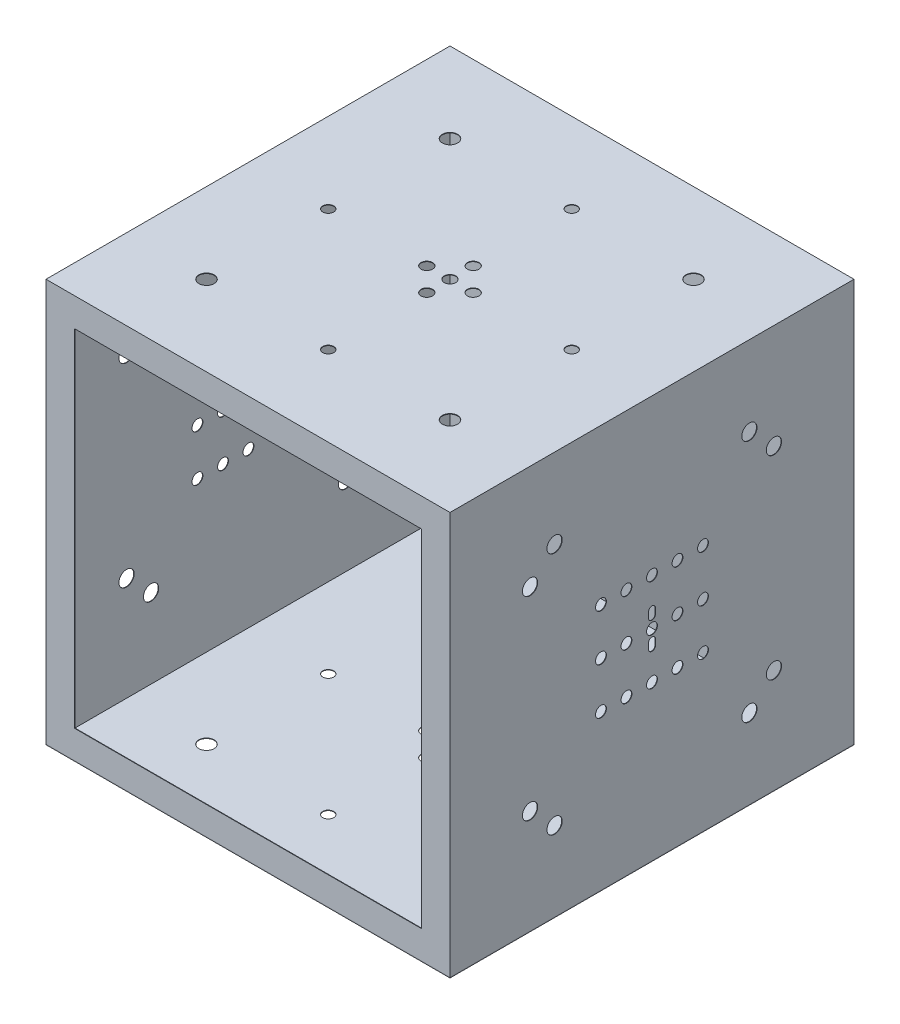
SolidWorks part; units mm, degrees
ref_plane "Front" through (0, 0, 0) normal (0, 0, 1) x (1, 0, 0)
ref_plane "Top" through (0, 0, 0) normal (0, 1, 0) x (1, 0, 0)
ref_plane "Right" through (0, 0, 0) normal (1, 0, 0) x (0, 0, -1)
sketch "Sketch1" plane through (0, 0, 0) normal (0, 0, 1) x (1, 0, 0)
  line L1 (-1742, 1738.5) -> (1742, 1738.5)
  line L2 (-1742, 1738.5) -> (-1742, -1738.5)
  line L3 (-1742, -1738.5) -> (1742, -1738.5)
  line L4 (1742, 1738.5) -> (1742, -1738.5)
  line L5 (-1742, 1738.5) -> (1742, -1738.5) construction
  line L6 (-1742, -1738.5) -> (1742, 1738.5) construction
  point P0 (0, 0)
  dimension "D1" = 3484
  dimension "D2" = 3477
extrude "Boss-Extrude1" add sketch "Sketch1" along normal blind 3484
shell "Shell1" thickness 4 removed face at (0, 0, 3484)
sketch "Sketch2" plane through (0, 0, 3484) normal (0, 0, 1) x (1, 0, 0)
  line L1 (1742, -1738.5) -> (-1742, -1738.5)
  line L2 (1742, -1738.5) -> (1742, 1738.5)
  line L3 (1742, 1738.5) -> (-1742, 1738.5)
  line L4 (-1742, -1738.5) -> (-1742, 1738.5)
  line L5 (1742, -1738.5) -> (-1742, 1738.5) construction
  line L6 (1742, 1738.5) -> (-1742, -1738.5) construction
  line L7 (-1495.5047, -1492.5) -> (1495.5047, -1492.5)
  line L8 (-1495.5047, -1492.5) -> (-1495.5047, 1492.5)
  line L9 (-1495.5047, 1492.5) -> (1495.5047, 1492.5)
  line L10 (1495.5047, -1492.5) -> (1495.5047, 1492.5)
  line L11 (-1495.5047, -1492.5) -> (1495.5047, 1492.5) construction
  line L12 (-1495.5047, 1492.5) -> (1495.5047, -1492.5) construction
  point P0 (0, 0)
  point P7 (0, 0)
  dimension "D1" = 246
extrude "Boss-Extrude2" add sketch "Sketch2" against normal blind 4
sketch "Sketch3" plane through (0, 1738.5, 0) normal (0, 1, 0) x (1, 0, 0)
  line L0 (-1742, -1742) -> (1742, -1742) construction
  line L1 (-1742, -3484) -> (-1742, 0) construction
  line L2 (1742, -3484) -> (1742, 0) construction
  line L3 (0, 0) -> (0, -3484) construction
  line L4 (1742, -3484) -> (-1742, -3484) construction
  line L5 (-1742, 0) -> (0, -1742) construction
  line L6 (0, -1742) -> (-200, -1742) construction
  circle A0 centre (0, -1742) radius 49.85
  circle A1 centre (-200, -1742) radius 49.85
  circle A2 centre (-1050, -1742) radius 46.75
  circle A3 centre (-1050, -692) radius 65.8
  circle A4 centre (1050, -692) radius 65.8
  circle A5 centre (200, -1742) radius 49.85
  circle A6 centre (1050, -1742) radius 46.75
  circle A7 centre (0, -2792) radius 46.75
  circle A8 centre (0, -1942) radius 49.85
  circle A9 centre (0, -1542) radius 49.85
  circle A10 centre (0, -692) radius 46.75
  circle A11 centre (1050, -2792) radius 65.8
  circle A12 centre (-1050, -2792) radius 65.8
  dimension "D1" = 99.7
  dimension "D4" = 93.5
  dimension "D6" = 131.6
  dimension "D3" = 200
  dimension "D5" = 1050
  dimension "D7" = 1050
  dimension "D2" = 2
extrude "Cut-Extrude1" cut sketch "Sketch3" against normal through all
sketch "Sketch4" plane through (0, 0, 0) normal (0, 0, -1) x (-1, 0, 0)
  line L0 (-1742, 0) -> (1742, 0) construction
  line L1 (-1742, -1738.5) -> (-1742, 1738.5) construction
  line L2 (1742, 1738.5) -> (1742, -1738.5) construction
  line L3 (0, 1738.5) -> (0, -1738.5) construction
  line L4 (-1742, 1738.5) -> (1742, 1738.5) construction
  line L5 (1742, -1738.5) -> (-1742, -1738.5) construction
  line L6 (0, 0) -> (-1742, 1738.5) construction
  circle A0 centre (0, 0) radius 91.2
  circle A1 centre (0, 140) radius 35.635
  circle A2 centre (-222, 382) radius 91.2
  circle A3 centre (-900, 898.1917) radius 65.8
  circle A4 centre (222, -382) radius 91.2
  circle A5 centre (0, -140) radius 35.635
  circle A6 centre (-900, -898.1917) radius 65.8
  circle A7 centre (900, -898.1917) radius 65.8
  circle A8 centre (900, 898.1917) radius 65.8
  dimension "D1" = 182.4
  dimension "D2" = 71.27
  dimension "D4" = 182.4
  dimension "D7" = 131.6
  dimension "D9" = 182.4
  dimension "D3" = 140
  dimension "D5" = 222
  dimension "D6" = 382
  dimension "D8" = 900
  dimension "D10" = 222
  dimension "D11" = 382
extrude "Cut-Extrude2" cut sketch "Sketch4" against normal through all
sketch "Sketch5" plane through (-1742, 0, 0) normal (-1, 0, 0) x (0, 0, 1)
  line L0 (0, 0) -> (3484, 0) construction
  line L1 (3484, 1738.5) -> (3484, -1738.5) construction
  line L2 (1742, 1738.5) -> (1742, -1738.5) construction
  line L3 (3484, 1738.5) -> (0, 1738.5) construction
  line L4 (3484, -1738.5) -> (0, -1738.5) construction
  line L5 (1742, 0) -> (0, 1738.5) construction
  line L6 (1742, 92.5) -> (1742, 140) construction
  line L7 (1712, 92.5) -> (1712, 140)
  line L8 (1772, 92.5) -> (1772, 140)
  line L9 (1742, 0) -> (1522, 0) construction
  line L10 (1742, 0) -> (1742, 400) construction
  line L11 (1742, -92.5) -> (1742, -140) construction
  line L12 (1712, -92.5) -> (1712, -140)
  line L13 (1772, -92.5) -> (1772, -140)
  circle A0 centre (1742, 0) radius 46.75
  arc A1 (1712, 92.5) -> (1772, 92.5) centre (1742, 92.5) ccw
  arc A2 (1772, 140) -> (1712, 140) centre (1742, 140) ccw
  circle A3 centre (1522, 0) radius 46.75
  circle A4 centre (1302, 0) radius 46.75
  circle A5 centre (1742, 400) radius 46.75
  circle A6 centre (1522, 400) radius 46.75
  circle A7 centre (1302, 400) radius 46.75
  circle A8 centre (902, 1050) radius 65.8
  circle A9 centre (690.3127, 837.8865) radius 65.8
  circle A10 centre (2582, 1050) radius 65.8
  circle A11 centre (2793.6873, 837.8865) radius 65.8
  circle A12 centre (2182, 0) radius 46.75
  circle A13 centre (1962, 0) radius 46.75
  circle A14 centre (1962, 400) radius 46.75
  circle A15 centre (2182, 400) radius 46.75
  circle A16 centre (2582, -1050) radius 65.8
  circle A17 centre (2793.6873, -837.8865) radius 65.8
  arc A18 (1712, -92.5) -> (1772, -92.5) centre (1742, -92.5) cw
  arc A19 (1772, -140) -> (1712, -140) centre (1742, -140) cw
  circle A20 centre (2182, -400) radius 46.75
  circle A21 centre (1962, -400) radius 46.75
  circle A22 centre (1742, -400) radius 46.75
  circle A23 centre (1522, -400) radius 46.75
  circle A24 centre (1302, -400) radius 46.75
  circle A25 centre (902, -1050) radius 65.8
  circle A26 centre (690.3127, -837.8865) radius 65.8
  point P17 (1742, 116.25)
  point P57 (1742, -116.25)
  dimension "D1" = 93.5
  dimension "D2" = 30
  dimension "D11" = 131.6
  dimension "D3" = 92.5
  dimension "D4" = 47.5
  dimension "D6" = 220
  dimension "D8" = 400
  dimension "D9" = 1050
  dimension "D10" = 840
  dimension "D5" = 3
  dimension "D7" = 2
extrude "Cut-Extrude3" cut sketch "Sketch5" against normal through all
split "Split1" bodies to split 107 resulting bodies 108 109 split by face at (0, -1734.5, 1991.85)
